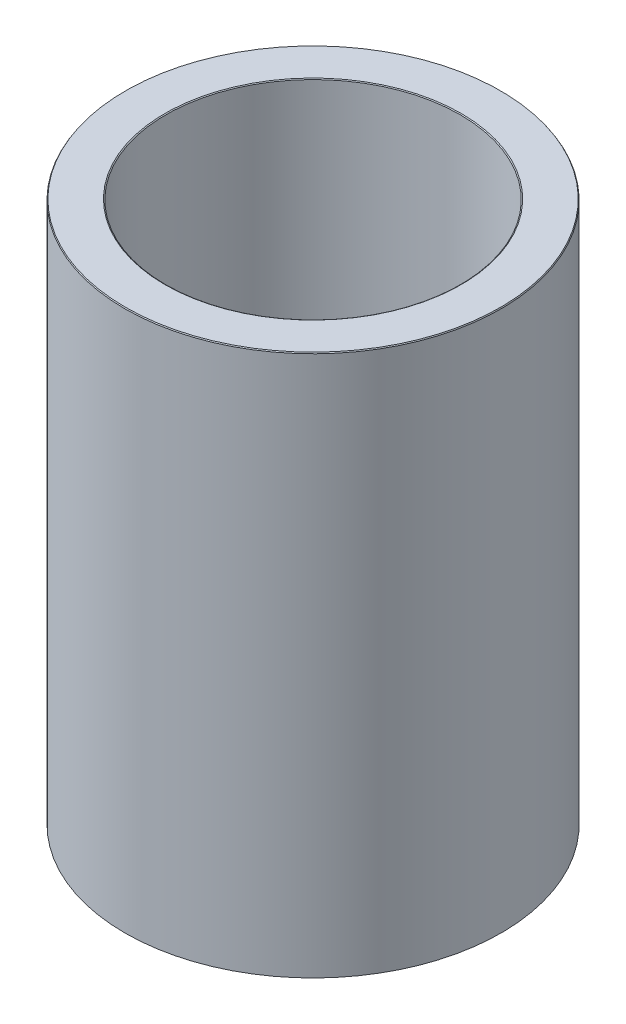
SolidWorks part; units mm, degrees
ref_plane "Front Plane" through (0, 0, 0) normal (0, 0, 1) x (1, 0, 0)
ref_plane "Top Plane" through (0, 0, 0) normal (0, 1, 0) x (1, 0, 0)
ref_plane "Right Plane" through (0, 0, 0) normal (1, 0, 0) x (0, 0, -1)
sketch "Sketch1" plane through (0, 0, 0) normal (0, 1, 0) x (1, 0, 0)
  circle A0 centre (0, 0) radius 55
  dimension "SLEEVE_OD" = 110
extrude "Boss-Extrude1" add sketch "Sketch1" along normal blind 158.4914
sketch "Sketch2" plane through (0, 0, 0) normal (0, 1, 0) x (1, 0, 0)
  circle A0 centre (0, 0) radius 43.0411
  dimension "BORE_D" = 86.0823
extrude "Cut-Extrude1" cut sketch "Sketch2" along normal through all
chamfer "Chamfer1" distance 0.2851 angle 32.843 4 edges at (0, 158.4914, 43.0411) (0, 0, 43.0411) (0, 0, 55) (0, 158.4914, 55) first distance on face at (0, 158.4914, 43.0411) first distance on face at (0, 0, 43.0411) first distance on face at (0, 158.4914, 55)
